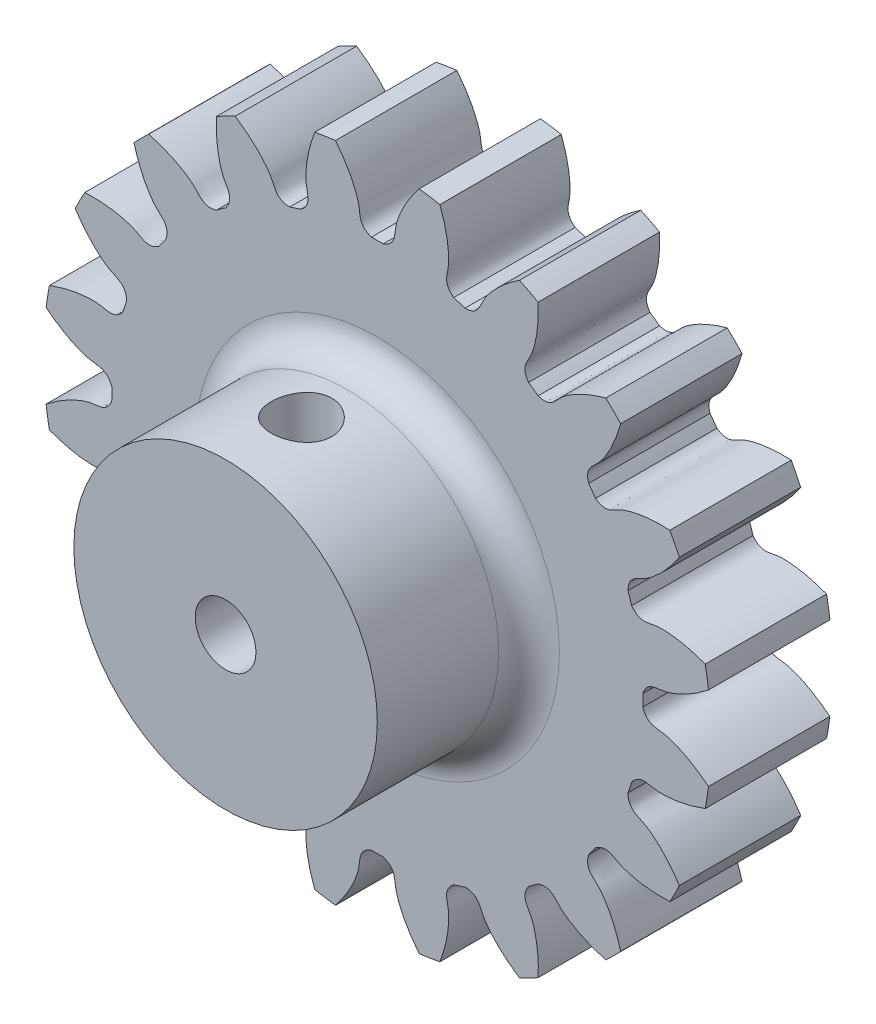
SolidWorks part; units mm, degrees
ref_plane "前视基准面" through (0, 0, 0) normal (0, 0, 1) x (1, 0, 0)
ref_plane "上视基准面" through (0, 0, 0) normal (0, 1, 0) x (1, 0, 0)
ref_plane "右视基准面" through (0, 0, 0) normal (1, 0, 0) x (0, 0, -1)
sketch "草图1" plane through (0, 0, 0) normal (0, 0, 1) x (1, 0, 0)
  circle A0 centre (0, 0) radius 11
extrude "凸台-拉伸1" add sketch "草图1" along normal blind 4
ref_axis "基准轴1" through (0, 0, -0.15) along (0, 0, 1)
sketch "草图2" plane through (0, 0, 0) normal (0, 0, 1) x (1, 0, 0)
  line L0 (0, 0) -> (0, 11) construction
  circle A0 centre (0, 0) radius 11 construction
  arc A1 (0.1933, 8.7479) -> (-0.1933, 8.7479) centre (0, 0) ccw
  arc A2 (3.1812, 12.4983) -> (-3.1812, 12.4983) centre (0, 0) ccw
  spline S0 degree 3 poles (0.1933, 8.7479) (0.6112, 8.8935) (0.5571, 9.1871) (0.6129, 9.47) (0.6189, 9.4976) (0.6263, 9.5286) (0.6353, 9.5632) (0.646, 9.6012) (0.6585, 9.6426) (0.673, 9.6873) (0.6897, 9.7352) (0.7086, 9.7863) (0.7299, 9.8406) (0.7537, 9.8978) (0.7801, 9.958) (0.8094, 10.0211) (0.8415, 10.087) (0.8767, 10.1556) (0.915, 10.2267) (0.9566, 10.3004) (1.0015, 10.3764) (1.05, 10.4548) (1.102, 10.5352) (1.1578, 10.6178) (1.2173, 10.7023) (1.2808, 10.7886) (1.3482, 10.8766) (1.4198, 10.9662) (1.4955, 11.0572) (1.5755, 11.1496) (1.6598, 11.2431) (1.7486, 11.3376) (1.8418, 11.4331) (1.9397, 11.5293) (2.0421, 11.6261) (2.1493, 11.7233) (2.2612, 11.8209) (2.378, 11.9186) (2.4996, 12.0163) (2.6261, 12.1139) (2.7575, 12.2112) (2.9415, 12.3416) (3.0839, 12.4363) (3.1812, 12.4983) knots 0 0 0 0 0.165916 0.170906 0.176664 0.183189 0.190482 0.198542 0.207371 0.216967 0.22733 0.238462 0.250361 0.263027 0.276462 0.290664 0.305634 0.321371 0.337876 0.355149 0.37319 0.391998 0.411574 0.431917 0.453028 0.474907 0.497554 0.520968 0.54515 0.570099 0.595817 0.622302 0.649554 0.677575 0.706363 0.735918 0.766242 0.797333 0.829191 0.861818 0.895212 0.929373 1 1 1 1
  spline S1 degree 3 poles (-0.1933, 8.7479) (-0.6112, 8.8935) (-0.5571, 9.1871) (-0.6129, 9.47) (-0.6189, 9.4976) (-0.6263, 9.5286) (-0.6353, 9.5632) (-0.646, 9.6012) (-0.6585, 9.6426) (-0.673, 9.6873) (-0.6897, 9.7352) (-0.7086, 9.7863) (-0.7299, 9.8406) (-0.7537, 9.8978) (-0.7801, 9.958) (-0.8094, 10.0211) (-0.8415, 10.087) (-0.8767, 10.1556) (-0.915, 10.2267) (-0.9566, 10.3004) (-1.0015, 10.3764) (-1.05, 10.4548) (-1.102, 10.5352) (-1.1578, 10.6178) (-1.2173, 10.7023) (-1.2808, 10.7886) (-1.3482, 10.8766) (-1.4198, 10.9662) (-1.4955, 11.0572) (-1.5755, 11.1496) (-1.6598, 11.2431) (-1.7486, 11.3376) (-1.8418, 11.4331) (-1.9397, 11.5293) (-2.0421, 11.6261) (-2.1493, 11.7233) (-2.2612, 11.8209) (-2.378, 11.9186) (-2.4996, 12.0163) (-2.6261, 12.1139) (-2.7575, 12.2112) (-2.9415, 12.3416) (-3.0839, 12.4363) (-3.1812, 12.4983) knots 0 0 0 0 0.165916 0.170906 0.176664 0.183189 0.190482 0.198542 0.207371 0.216967 0.22733 0.238462 0.250361 0.263027 0.276462 0.290664 0.305634 0.321371 0.337876 0.355149 0.37319 0.391998 0.411574 0.431917 0.453028 0.474907 0.497554 0.520968 0.54515 0.570099 0.595817 0.622302 0.649554 0.677575 0.706363 0.735918 0.766242 0.797333 0.829191 0.861818 0.895212 0.929373 1 1 1 1
extrude "切除-拉伸1" cut sketch "草图2" along normal through all
pattern_circular "阵列(圆周)1" count 20 every 18 about axis through (0, 0, -0.15) along (0, 0, 1) of "切除-拉伸1"
sketch "草图3" plane through (0, 0, 0) normal (0, 0, 1) x (1, 0, 0)
  circle A0 centre (0, 0) radius 10 construction
  dimension "Dn" = 20
sketch "草图5" plane through (0, 0, 4) normal (0, 0, 1) x (1, 0, 0)
  circle A0 centre (0, 0) radius 5
  dimension "D1" = 10
extrude "凸台-拉伸2" add sketch "草图5" along normal blind 5
sketch "草图6" plane through (0, 0, 9) normal (0, 0, 1) x (1, 0, 0)
  circle A0 centre (0, 0) radius 1
  dimension "D1" = 2
extrude "切除-拉伸2" cut sketch "草图6" against normal through all both and the other way through all
sketch "草图7" plane through (0, 0, 0) normal (0, 1, 0) x (1, 0, 0)
  line L0 (0, -6.5) -> (0, -9) construction
  line L1 (-5, -9) -> (5, -9) construction
  circle A0 centre (0, -6.5) radius 1
  dimension "D1" = 2
  dimension "D2" = 2.5
extrude "切除-拉伸3" cut sketch "草图7" against normal through all both and the other way through all
fillet "圆角1" radius 1 1 edges at (5, 0, 4)
